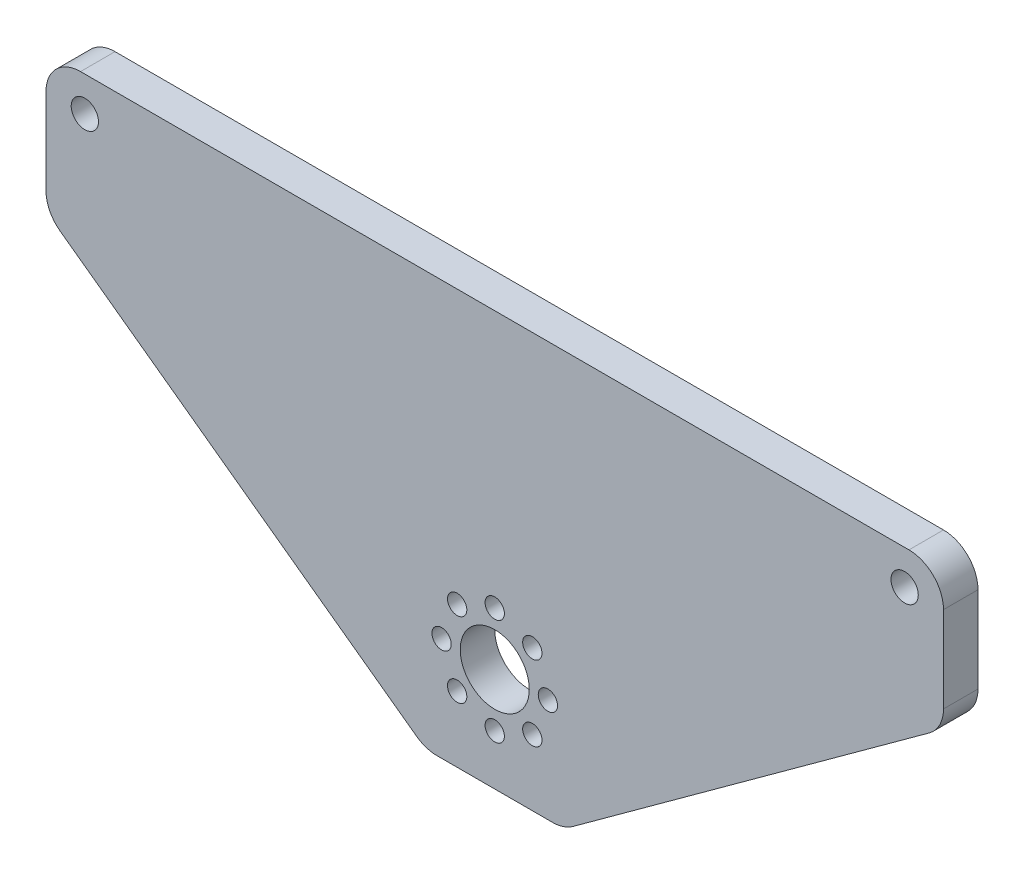
SolidWorks part; units mm, degrees
material "6061-T6 (SS)"
ref_plane "Front Plane" through (0, 0, 0) normal (0, 0, 1) x (1, 0, 0)
ref_plane "Top Plane" through (0, 0, 0) normal (0, 1, 0) x (1, 0, 0)
ref_plane "Right Plane" through (0, 0, 0) normal (1, 0, 0) x (0, 0, -1)
sketch "Sketch1" plane through (0, 0, 0) normal (0, 0, 1) x (1, 0, 0)
  line L1 (82.55, 38.1) -> (-82.55, 38.1)
  line L2 (82.55, 38.1) -> (82.55, -38.1)
  line L3 (82.55, -38.1) -> (-82.55, -38.1)
  line L4 (-82.55, 38.1) -> (-82.55, -38.1)
  line L5 (82.55, 38.1) -> (-82.55, -38.1) construction
  line L6 (82.55, -38.1) -> (-82.55, 38.1) construction
  circle A0 centre (0, -19.05) radius 6.35
  circle A1 centre (-75.4063, 31.75) radius 2.5083
  circle A2 centre (75.4062, 31.75) radius 2.5083
  point P0 (0, 0)
  dimension "D3" = 12.7
  dimension "D4" = 75.4062
  dimension "D8" = 5.0165
  dimension "D9" = 5.0165
  dimension "D10" = 19.05
  dimension "D1" = 165.1
  dimension "D2" = 76.2
  dimension "D5" = 75.4062
  dimension "D6" = 50.8
  dimension "D7" = 50.8
extrude "Boss-Extrude1" add sketch "Sketch1" along normal blind 6.35
sketch "Sketch2" plane through (0, 0, 0) normal (0, 0, -1) x (-1, 0, 0)
  line L0 (12.7, -38.1) -> (82.55, 12.7)
  line L1 (82.55, -38.1) -> (-82.55, -38.1) construction
  line L2 (82.55, 38.1) -> (82.55, -38.1) construction
  line L3 (82.55, 12.7) -> (82.55, -38.1)
  line L4 (82.55, -38.1) -> (12.7, -38.1)
  line L5 (-82.55, -38.1) -> (-82.55, 12.7)
  line L6 (-82.55, -38.1) -> (-82.55, 38.1) construction
  line L7 (-82.55, 12.7) -> (-12.7, -38.1)
  line L8 (-12.7, -38.1) -> (-82.55, -38.1)
  dimension "D1" = 69.85
  dimension "D2" = 69.85
  dimension "D3" = 50.8
  dimension "D4" = 50.8
extrude "Cut-Extrude1" cut sketch "Sketch2" against normal blind 6.35
fillet "Fillet1" radius 6.35 6 edges at (-82.55, 38.1, 3.175) (82.55, 12.7, 3.175) (-82.55, 12.7, 3.175) (-12.7, -38.1, 3.175) (12.7, -38.1, 3.175) (82.55, 38.1, 3.175)
sketch "Sketch3" plane through (0, 0, 0) normal (0, 0, -1) x (-1, 0, 0)
  circle A0 centre (0, -9.271) radius 1.778
  circle A1 centre (0, -19.05) radius 6.35 construction
  dimension "D1" = 3.556
  dimension "D2" = 9.779
extrude "Cut-Extrude2" cut sketch "Sketch3" against normal blind 6.35
pattern_circular "CirPattern1" count 8 over 360 about axis through (0, -19.05, 0) along (0, 0, 1) of "Cut-Extrude2"
